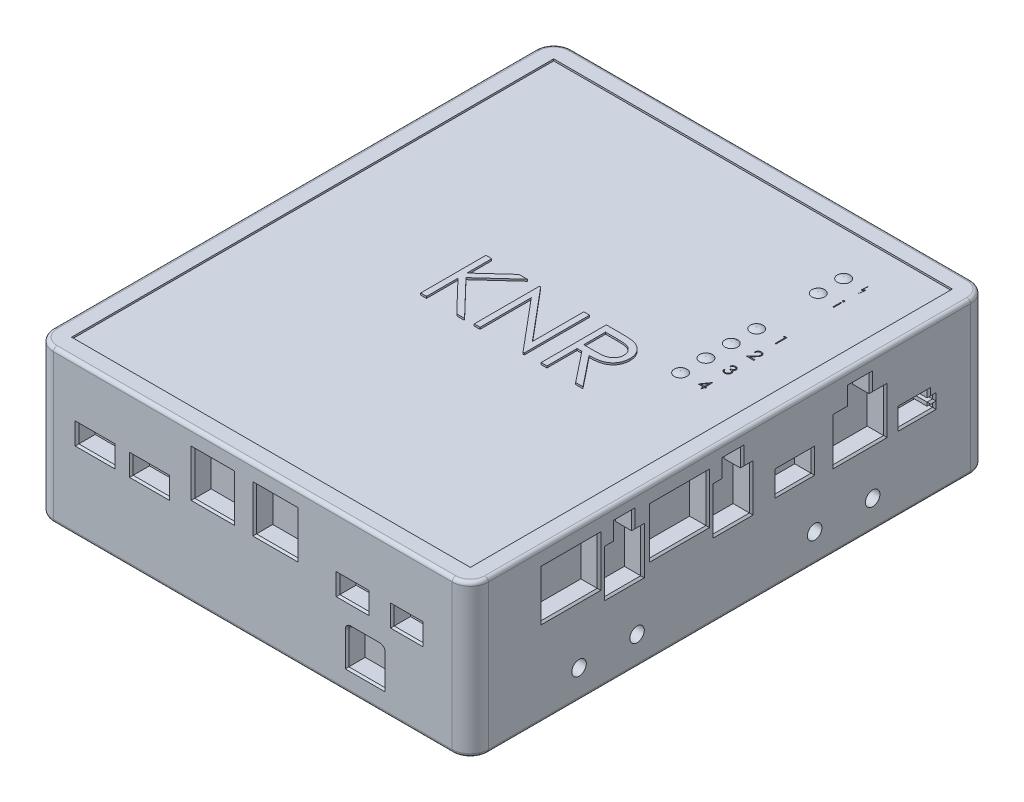
SolidWorks part; units mm, degrees
ref_plane "前基準面" through (0, 0, 0) normal (0, 0, 1) x (1, 0, 0)
ref_plane "上基準面" through (0, 0, 0) normal (0, 1, 0) x (1, 0, 0)
ref_plane "右基準面" through (0, 0, 0) normal (1, 0, 0) x (0, 0, -1)
sketch "草圖1" plane through (0, 0, 0) normal (0, 1, 0) x (1, 0, 0)
  line L1 (0, 0) -> (-120, 0)
  line L2 (0, 0) -> (0, -143)
  line L3 (0, -143) -> (-120, -143)
  line L4 (-120, 0) -> (-120, -143)
  dimension "D1" = 120
  dimension "D2" = 143
extrude "填料-伸長1" add sketch "草圖1" along normal blind 42
fillet "圓角1" radius 5 4 edges at (0, 21, 0) (-120, 21, 0) (-120, 21, 143) (0, 21, 143)
fillet "圓角2" radius 1 16 edges at (-1.4645, 0, 1.4645) (0, 0, 71.5) (-1.4645, 0, 141.5355) (-60, 0, 143) (-118.5355, 0, 141.5355) (-120, 0, 71.5) (-118.5355, 0, 1.4645) (-1.4645, 42, 1.4645) (0, 42, 71.5) (-1.4645, 42, 141.5355) (-60, 42, 143) (-118.5355, 42, 141.5355) (-120, 42, 71.5) (-118.5355, 42, 1.4645) (-60, 0, 0) (-60, 42, 0)
sketch "草圖2" plane through (0, 42, 0) normal (0, 1, 0) x (1, 0, 0)
  line L0 (-115, 0) -> (-5, 0) construction
  line L1 (-115, -5) -> (-5, -5)
  line L2 (-115, -5) -> (-115, -138)
  line L3 (-115, -138) -> (-5, -138)
  line L4 (-5, -5) -> (-5, -138)
  line L5 (-120, -138) -> (-120, -5) construction
  line L6 (0, -5) -> (0, -138) construction
  line L7 (-5, -143) -> (-115, -143) construction
  dimension "D1" = 5
  dimension "D2" = 5
  dimension "D3" = 5
  dimension "D4" = 5
extrude "除料-伸長1" cut sketch "草圖2" against normal blind 0.5
sketch "草圖3" plane through (0, 41.5, 0) normal (0, 1, 0) x (1, 0, 0)
  text T0 "KNR" font "Century Gothic" height 18
extrude "填料-伸長2" add sketch "草圖3" along normal blind 0.5
sketch "草圖4" plane through (0, 41.5, 0) normal (0, 1, 0) x (1, 0, 0)
  line L0 (-5, -138) -> (-5, -5) construction
  line L1 (-5, -5) -> (-115, -5) construction
  circle A0 centre (-23, -17) radius 1.75
  circle A1 centre (-23, -24) radius 1.75
  circle A2 centre (-23, -41) radius 1.75
  circle A3 centre (-23, -48) radius 1.75
  circle A4 centre (-23, -55) radius 1.75
  circle A5 centre (-23, -62) radius 1.75
  dimension "D1" = 18
  dimension "D3" = 3.5
  dimension "D2" = 12
  dimension "D4" = 2
  dimension "D5" = 2
  dimension "D6" = 4
extrude "填料-伸長3" add sketch "草圖4" along normal blind 0.5
fillet "圓角3" radius 3 6 edges at (-23, 42, 18.75) (-23, 42, 63.75) (-23, 42, 56.75) (-23, 42, 49.75) (-23, 42, 42.75) (-23, 42, 25.75)
sketch "草圖6" plane through (0, 41.5, 0) normal (0, 1, 0) x (1, 0, 0)
  circle A0 centre (-23, -17) radius 0.0917 construction
  circle A2 centre (-23, -41) radius 0.0917 construction
  text T0 "ㄣ" font "Century Gothic" height 3
  text T1 "i" font "Century Gothic" height 3
  text T2 "1\r\n2\r\n3\r\n4" font "Century Gothic" height 3
  dimension "D2" = 5
  dimension "D1" = 5
extrude "除料-伸長2" cut sketch "草圖6" against normal blind 0.5
sketch "草圖7" plane through (0, 0, 0) normal (1, 0, 0) x (0, 0, -1)
  line L0 (-143, 1) -> (-143, 41) construction
  line L1 (-123, 37) -> (-107.5, 37)
  line L2 (-123, 37) -> (-123, 24)
  line L3 (-123, 24) -> (-107.5, 24)
  line L4 (-107.5, 37) -> (-107.5, 24)
  line L5 (-138, 42) -> (-5, 42) construction
  line L6 (-105.5, 33) -> (-105.5, 21)
  line L7 (-105.5, 21) -> (-95.5, 21)
  line L8 (-95.5, 21) -> (-95.5, 33)
  line L9 (-95.5, 33) -> (-98, 33)
  line L10 (-98, 33) -> (-98, 38)
  line L11 (-98, 38) -> (-103, 38)
  line L12 (-103, 38) -> (-103, 33)
  line L13 (-103, 33) -> (-105.5, 33)
  line L14 (-93, 24) -> (-77.5, 24)
  line L15 (-93, 37) -> (-93, 24)
  line L16 (-93, 37) -> (-77.5, 37)
  line L17 (-77.5, 37) -> (-77.5, 24)
  line L18 (-75.5, 33) -> (-75.5, 21)
  line L19 (-73, 33) -> (-75.5, 33)
  line L20 (-73, 38) -> (-73, 33)
  line L21 (-68, 38) -> (-73, 38)
  line L22 (-68, 33) -> (-68, 38)
  line L23 (-65.5, 33) -> (-68, 33)
  line L24 (-65.5, 21) -> (-65.5, 33)
  line L25 (-75.5, 21) -> (-65.5, 21)
  line L26 (-42.5, 21) -> (-42.5, 33)
  line L27 (-58.5, 28) -> (-48.5, 28)
  line L28 (-58.5, 28) -> (-58.5, 22)
  line L29 (-58.5, 22) -> (-48.5, 22)
  line L30 (-48.5, 28) -> (-48.5, 22)
  line L31 (-42.5, 33) -> (-38.5, 33)
  line L32 (-38.5, 33) -> (-38.5, 38)
  line L33 (-38.5, 38) -> (-32.5, 38)
  line L34 (-32.5, 38) -> (-32.5, 33)
  line L35 (-32.5, 33) -> (-28.5, 33)
  line L36 (-28.5, 33) -> (-28.5, 21)
  line L37 (-28.5, 21) -> (-42.5, 21)
  line L38 (-16.5, 21) -> (-15, 21)
  line L39 (-24.5, 26) -> (-16.5, 26)
  line L40 (-24.5, 26) -> (-24.5, 21)
  line L41 (-24.5, 21) -> (-16.5, 21)
  line L42 (-16.5, 26) -> (-16.5, 24)
  line L43 (-15, 21) -> (-15, 22)
  line L44 (-15, 22) -> (-16.5, 22)
  line L45 (-15, 24) -> (-16.5, 24)
  line L46 (-15, 23) -> (-15, 24)
  line L47 (-16.5, 23) -> (-15, 23)
  line L48 (-16.5, 23) -> (-16.5, 22)
  dimension "D1" = 20
  dimension "D2" = 5
  dimension "D3" = 13
  dimension "D4" = 15.5
  dimension "D5" = 2
  dimension "D6" = 4
  dimension "D7" = 9
  dimension "D8" = 4.5
  dimension "D9" = 5
  dimension "D10" = 10
  dimension "D11" = 21
  dimension "D12" = 2
  dimension "D13" = 7
  dimension "D14" = 20
  dimension "D15" = 6
  dimension "D16" = 10
  dimension "D17" = 6
  dimension "D18" = 4
  dimension "D19" = 4
  dimension "D20" = 14
  dimension "D21" = 4
  dimension "D22" = 1.5
  dimension "D23" = 1
  dimension "D24" = 8
  dimension "D25" = 5
  dimension "D26" = 2
extrude "除料-伸長3" cut sketch "草圖7" against normal blind 5
chamfer "導角1" distance 0.5 angle 45 46 edges at (0, 26, 20.5) (0, 23.5, 24.5) (0, 25, 16.5) (0, 24, 15.75) (0, 23.5, 15) (0, 23, 15.75) (0, 22.5, 16.5) (0, 22, 15.75) (0, 21.5, 15) (0, 21, 19.75) (0, 21, 35.5) (0, 27, 28.5) (0, 33, 30.5) (0, 35.5, 32.5) (0, 38, 35.5) (0, 35.5, 38.5) (0, 33, 40.5) (0, 27, 42.5) (0, 22, 53.5) (0, 25, 48.5) (0, 28, 53.5) (0, 25, 58.5) (0, 21, 70.5) (0, 27, 65.5) (0, 33, 66.75) (0, 35.5, 68) (0, 38, 70.5) (0, 35.5, 73) (0, 27, 75.5) (0, 33, 74.25) (0, 24, 85.25) (0, 30.5, 77.5) (0, 37, 85.25) (0, 30.5, 93) (0, 33, 96.75) (0, 27, 95.5) (0, 21, 100.5) (0, 35.5, 98) (0, 38, 100.5) (0, 35.5, 103) (0, 33, 104.25) (0, 27, 105.5) (0, 24, 115.25) (0, 30.5, 107.5) (0, 30.5, 123) (0, 37, 115.25)
sketch "草圖8" plane through (0, 0, 0) normal (0, 0, -1) x (-1, 0, 0)
  line L0 (0, 1) -> (0, 41) construction
  line L1 (26, 14) -> (39, 14)
  line L2 (26, 14) -> (26, 8)
  line L3 (26, 8) -> (39, 8)
  line L4 (39, 14) -> (39, 8)
  line L5 (115, 0) -> (5, 0) construction
  line L6 (120, 41) -> (120, 1) construction
  line L7 (23, 25.5) -> (34, 25.5)
  line L8 (23, 25.5) -> (23, 22)
  line L9 (23, 22) -> (34, 22)
  line L10 (34, 25.5) -> (34, 22)
  line L11 (43, 18) -> (55, 18)
  line L12 (43, 18) -> (43, 7)
  line L13 (43, 7) -> (55, 7)
  line L14 (55, 18) -> (55, 7)
  line L15 (59, 18.5) -> (68, 18.5)
  line L16 (59, 18.5) -> (59, 6.5)
  line L17 (59, 6.5) -> (68, 6.5)
  line L18 (68, 18.5) -> (68, 6.5)
  line L19 (37, 20) -> (58, 20)
  line L20 (37, 20) -> (37, 30)
  line L21 (37, 30) -> (58, 30)
  line L22 (58, 20) -> (58, 30)
  line L23 (61, 26.5) -> (68, 26.5)
  line L24 (61, 26.5) -> (61, 21.5)
  line L25 (61, 21.5) -> (68, 21.5)
  line L26 (68, 26.5) -> (68, 21.5)
  line L27 (93, 33) -> (99.5, 33)
  line L28 (93, 33) -> (93, 23)
  line L29 (93, 23) -> (99.5, 23)
  line L30 (99.5, 33) -> (99.5, 23)
  line L31 (5, 42) -> (115, 42) construction
  line L33 (102, 27) -> (108, 27)
  line L34 (102, 27) -> (102, 22)
  line L35 (102, 22) -> (108, 22)
  line L36 (108, 27) -> (108, 22)
  circle A0 centre (79, 11) radius 1.5
  circle A1 centre (76, 23.5) radius 1.5
  dimension "D17" = 3
  dimension "D28" = 3
  dimension "D1" = 26
  dimension "D2" = 13
  dimension "D3" = 8
  dimension "D4" = 6
  dimension "D5" = 23
  dimension "D6" = 11
  dimension "D7" = 3.5
  dimension "D8" = 8
  dimension "D9" = 4
  dimension "D10" = 1
  dimension "D11" = 12
  dimension "D12" = 11
  dimension "D13" = 4
  dimension "D14" = 12
  dimension "D15" = 0.5
  dimension "D16" = 9
  dimension "D18" = 11
  dimension "D19" = 11
  dimension "D20" = 2
  dimension "D21" = 3
  dimension "D22" = 10
  dimension "D23" = 21
  dimension "D24" = 3
  dimension "D25" = 1.5
  dimension "D26" = 5
  dimension "D27" = 7
  dimension "D29" = 8
  dimension "D30" = 2
  dimension "D31" = 27
  dimension "D32" = 19
  dimension "D33" = 6.5
  dimension "D34" = 10
  dimension "D35" = 2.5
  dimension "D36" = 1
  dimension "D37" = 5
  dimension "D38" = 6
extrude "除料-伸長4" cut sketch "草圖8" against normal blind 5
sketch "草圖10" plane through (0, 0, 5) normal (0, 0, -1) x (-1, 0, 0)
  circle A0 centre (76, 23.5) radius 1.5
extrude "填料-伸長4" add sketch "草圖10" along normal blind 6
fillet "圓角4" radius 1.5 1 edges at (-77.5, 23.5, -1)
chamfer "導角2" distance 0.8 angle 45 33 edges at (-28.5, 25.5, 0) (-105, 22, 0) (-108, 24.5, 0) (-105, 27, 0) (-102, 24.5, 0) (-96.25, 33, 0) (-93, 28, 0) (-99.5, 28, 0) (-96.25, 23, 0) (-80.5, 11, 0) (-68, 24, 0) (-64.5, 26.5, 0) (-61, 24, 0) (-64.5, 21.5, 0) (-63.5, 6.5, 0) (-59, 12.5, 0) (-68, 12.5, 0) (-63.5, 18.5, 0) (-26, 11, 0) (-32.5, 14, 0) (-39, 11, 0) (-32.5, 8, 0) (-49, 7, 0) (-43, 12.5, 0) (-55, 12.5, 0) (-49, 18, 0) (-58, 25, 0) (-47.5, 20, 0) (-37, 25, 0) (-47.5, 30, 0) (-34, 23.75, 0) (-28.5, 22, 0) (-23, 23.75, 0)
sketch "草圖11" plane through (-120, 0, 0) normal (-1, 0, 0) x (0, 0, 1)
  line L0 (0, 1) -> (0, 41) construction
  line L1 (20, 34) -> (56, 34)
  line L2 (20, 34) -> (20, 22)
  line L3 (20, 22) -> (56, 22)
  line L4 (56, 34) -> (56, 22)
  line L5 (5, 42) -> (138, 42) construction
  line L6 (105, 24) -> (105, 37)
  line L7 (59, 22.5) -> (71, 22.5)
  line L8 (59, 22.5) -> (59, 28)
  line L9 (59, 28) -> (71, 28)
  line L10 (71, 22.5) -> (71, 28)
  line L11 (75, 37) -> (90.5, 37)
  line L12 (105, 37) -> (120.5, 37)
  line L13 (120.5, 37) -> (120.5, 24)
  line L14 (120.5, 24) -> (105, 24)
  line L15 (90.5, 37) -> (90.5, 24)
  line L16 (90.5, 24) -> (75, 24)
  line L17 (75, 24) -> (75, 37)
  line L18 (123, 33) -> (123, 21)
  line L19 (123, 21) -> (133, 21)
  line L20 (133, 21) -> (133, 33)
  line L21 (133, 33) -> (130.5, 33)
  line L22 (130.5, 33) -> (130.5, 38)
  line L23 (125.5, 38) -> (125.5, 33)
  line L24 (125.5, 33) -> (123, 33)
  line L25 (130.5, 38) -> (125.5, 38)
  line L34 (103, 33) -> (100.5, 33)
  line L35 (103, 21) -> (103, 33)
  line L36 (93, 21) -> (103, 21)
  line L37 (93, 33) -> (93, 21)
  line L38 (95.5, 33) -> (93, 33)
  line L39 (95.5, 38) -> (95.5, 33)
  line L40 (100.5, 38) -> (95.5, 38)
  line L41 (100.5, 33) -> (100.5, 38)
  dimension "D1" = 20
  dimension "D2" = 20
  dimension "D3" = 12
  dimension "D4" = 36
  dimension "D5" = 5.5
  dimension "D6" = 0.5
  dimension "D7" = 3
  dimension "D8" = 12
  dimension "D9" = 4
  dimension "D10" = 15.5
  dimension "D11" = 13
  dimension "D12" = 18
  dimension "D13" = 2.5
  dimension "D14" = 12
  dimension "D15" = 5
  dimension "D16" = 2.5
  dimension "D17" = 9
  dimension "D18" = 4
  dimension "D19" = 10
  dimension "D20" = 2
extrude "除料-伸長5" cut sketch "草圖11" against normal blind 5
sketch "草圖13" plane through (0, 0, 143) normal (0, 0, 1) x (1, 0, 0)
  line L0 (-115, 42) -> (-5, 42) construction
  line L1 (-108.5, 27) -> (-98.5, 27)
  line L2 (-108.5, 27) -> (-108.5, 22)
  line L3 (-108.5, 22) -> (-98.5, 22)
  line L4 (-98.5, 27) -> (-98.5, 22)
  line L5 (-120, 1) -> (-120, 41) construction
  line L6 (-93.5, 27) -> (-83.5, 27)
  line L7 (-93.5, 27) -> (-93.5, 22)
  line L8 (-83.5, 27) -> (-83.5, 22)
  line L9 (-93.5, 22) -> (-83.5, 22)
  line L10 (-59.5, 37) -> (-59.5, 25)
  line L11 (-76.5, 37) -> (-65.5, 37)
  line L12 (-76.5, 37) -> (-76.5, 25)
  line L13 (-76.5, 25) -> (-65.5, 25)
  line L14 (-65.5, 37) -> (-65.5, 25)
  line L15 (-59.5, 37) -> (-48, 37)
  line L16 (-59.5, 25) -> (-48, 25)
  line L17 (-48, 25) -> (-48, 37)
  line L18 (-36.5, 27) -> (-28.5, 27)
  line L19 (-21.5, 27) -> (-13.5, 27)
  line L20 (-21.5, 27) -> (-21.5, 22)
  line L21 (-21.5, 22) -> (-13.5, 22)
  line L22 (-13.5, 27) -> (-13.5, 22)
  line L23 (-36.5, 27) -> (-36.5, 22)
  line L24 (-28.5, 27) -> (-28.5, 22)
  line L25 (-36.5, 22) -> (-28.5, 22)
  line L26 (-5, 0) -> (-115, 0) construction
  line L27 (-33, 16) -> (-25, 16)
  line L28 (-34, 15) -> (-34, 6)
  line L29 (-34, 6) -> (-24, 6)
  line L30 (-24, 15) -> (-24, 6)
  line L31 (0, 41) -> (0, 1) construction
  arc A0 (-25, 16) -> (-24, 15) centre (-25, 15) cw
  arc A1 (-33, 16) -> (-34, 15) centre (-33, 15) ccw
  point P39 (-24, 16)
  point P42 (-34, 16)
  dimension "D24" = 1
  dimension "D1" = 10
  dimension "D2" = 20
  dimension "D3" = 11.5
  dimension "D4" = 5
  dimension "D6" = 7
  dimension "D7" = 5
  dimension "D8" = 17
  dimension "D9" = 11
  dimension "D10" = 12
  dimension "D12" = 6
  dimension "D13" = 5
  dimension "D11" = 12
  dimension "D14" = 11.5
  dimension "D15" = 21.5
  dimension "D16" = 8
  dimension "D17" = 20
  dimension "D18" = 5
  dimension "D20" = 6
  dimension "D21" = 10
  dimension "D22" = 34
  dimension "D23" = 10
  dimension "D5" = 2
  dimension "D19" = 2
extrude "除料-伸長6" cut sketch "草圖13" against normal blind 5
chamfer "導角3" distance 0.5 angle 45 30 edges at (-29, 6, 143) (-24, 10.5, 143) (-24.2929, 15.7071, 143) (-29, 16, 143) (-33.7071, 15.7071, 143) (-34, 10.5, 143) (-17.5, 22, 143) (-13.5, 24.5, 143) (-17.5, 27, 143) (-21.5, 24.5, 143) (-28.5, 24.5, 143) (-32.5, 27, 143) (-36.5, 24.5, 143) (-32.5, 22, 143) (-53.75, 25, 143) (-48, 31, 143) (-53.75, 37, 143) (-59.5, 31, 143) (-71, 37, 143) (-65.5, 31, 143) (-76.5, 31, 143) (-71, 25, 143) (-83.5, 24.5, 143) (-88.5, 27, 143) (-93.5, 24.5, 143) (-88.5, 22, 143) (-98.5, 24.5, 143) (-103.5, 27, 143) (-108.5, 24.5, 143) (-103.5, 22, 143)
sketch "草圖14" plane through (-120, 0, 0) normal (-1, 0, 0) x (0, 0, 1)
  line L0 (138, 0) -> (5, 0) construction
  line L1 (0, 1) -> (0, 41) construction
  circle A0 centre (32, 8) radius 2
  circle A1 centre (48, 8) radius 2
  circle A2 centre (97, 8) radius 2
  circle A3 centre (113, 8) radius 2
  dimension "D1" = 8
  dimension "D3" = 4
  dimension "D2" = 32
  dimension "D4" = 2
  dimension "D5" = 2
extrude "除料-伸長7" cut sketch "草圖14" against normal blind 5
sketch "草圖15" plane through (0, 0, 0) normal (1, 0, 0) x (0, 0, -1)
  circle A0 centre (-32, 8) radius 2 construction
  circle A1 centre (-32, 8) radius 2
  circle A2 centre (-48, 8) radius 2 construction
  circle A3 centre (-48, 8) radius 2
  circle A5 centre (-97, 8) radius 2
  circle A6 centre (-97, 8) radius 2
  circle A7 centre (-113, 8) radius 2
  circle A8 centre (-113, 8) radius 2
  dimension "D1" = 0
  dimension "D2" = 0
extrude "除料-伸長8" cut sketch "草圖15" against normal blind 5
sketch "草圖16" plane through (0, 0, 0) normal (0, -1, 0) x (1, 0, 0)
  line L0 (0, 138) -> (0, 5) construction
  line L2 (-115, 143) -> (-5, 143) construction
  line L3 (-5, 0) -> (-115, 0) construction
  line L4 (-120, 5) -> (-120, 138) construction
  circle A0 centre (-8, 113) radius 2
  circle A1 centre (-8, 97) radius 2
  circle A2 centre (-112, 97) radius 2
  circle A3 centre (-112, 113) radius 2
  circle A4 centre (-112, 33) radius 2
  circle A5 centre (-112, 49) radius 2
  circle A6 centre (-8, 33) radius 2
  circle A7 centre (-8, 49) radius 2
  circle A8 centre (-81, 8) radius 2
  circle A9 centre (-65, 8) radius 2
  circle A10 centre (-49, 8) radius 2
  circle A11 centre (-33, 8) radius 2
  dimension "D1" = 4
  dimension "D9" = 4
  dimension "D2" = 8
  dimension "D3" = 30
  dimension "D7" = 8
  dimension "D8" = 39
  dimension "D4" = 2
  dimension "D5" = 2
  dimension "D6" = 2
  dimension "D10" = 2
  dimension "D11" = 2
extrude "除料-伸長9" cut sketch "草圖16" against normal blind 5
